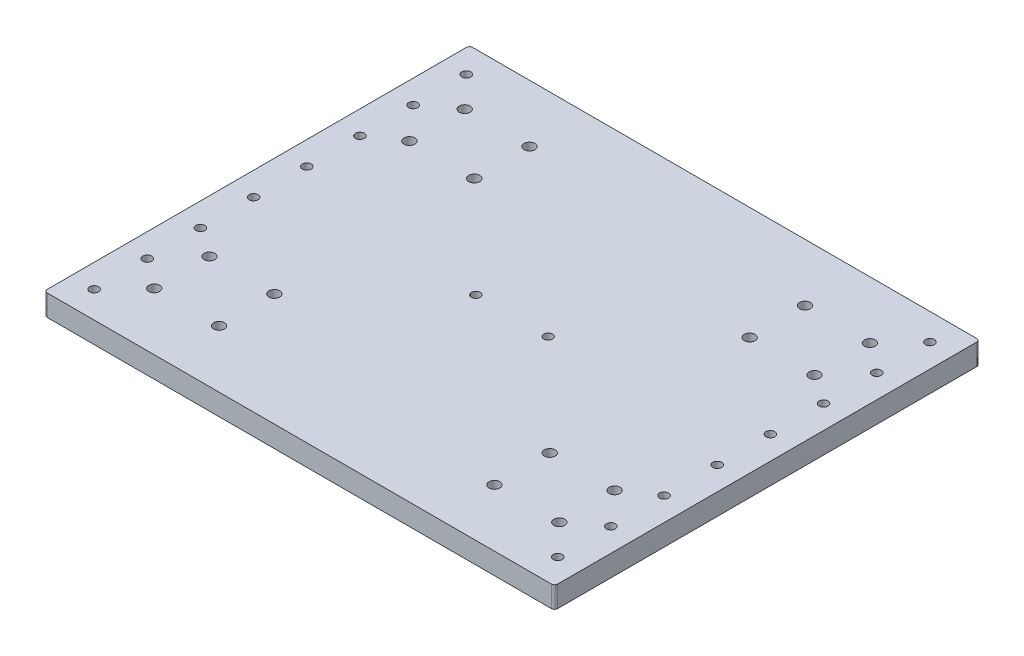
SolidWorks part; units mm, degrees
ref_plane "Front Plane" through (0, 0, 0) normal (0, 0, 1) x (1, 0, 0)
ref_plane "Top Plane" through (0, 0, 0) normal (0, 1, 0) x (1, 0, 0)
ref_plane "Right Plane" through (0, 0, 0) normal (1, 0, 0) x (0, 0, -1)
sketch "Sketch1" plane through (0, 0, 0) normal (0, 1, 0) x (1, 0, 0)
  line L1 (-120, -100) -> (120, -100)
  line L2 (-120, -100) -> (-120, 100)
  line L3 (-120, 100) -> (120, 100)
  line L4 (120, -100) -> (120, 100)
  line L5 (-120, -100) -> (120, 100) construction
  line L6 (-120, 100) -> (120, -100) construction
  point P0 (0, 0)
  dimension "D1" = 240
  dimension "D2" = 200
extrude "Boss-Extrude1" add sketch "Sketch1" along normal mid plane 10
sketch "Sketch2" plane through (0, 5, 0) normal (0, 1, 0) x (1, 0, 0)
  line L5 (-80, 100) -> (-80, -100)
  line L6 (-80, 100) -> (-80, -100) construction
  line L8 (80, -100) -> (80, 100)
  line L9 (80, -100) -> (80, 100) construction
  line L11 (120, 60) -> (-120, 60)
  line L12 (120, 60) -> (-120, 60) construction
  line L14 (-120, -60) -> (120, -60)
  line L15 (-120, -60) -> (120, -60) construction
  line L16 (-95.25, 73) -> (-64.75, 73) construction
  line L17 (-95.25, 73) -> (-95.25, 47) construction
  line L18 (-95.25, 47) -> (-64.75, 47) construction
  line L19 (-64.75, 73) -> (-64.75, 47) construction
  line L20 (-95.25, 73) -> (-64.75, 47) construction
  line L21 (-95.25, 47) -> (-64.75, 73) construction
  line L22 (64.75, 47) -> (95.25, 47) construction
  line L23 (64.75, 47) -> (64.75, 73) construction
  line L24 (64.75, 73) -> (95.25, 73) construction
  line L25 (95.25, 47) -> (95.25, 73) construction
  line L26 (64.75, 47) -> (95.25, 73) construction
  line L27 (64.75, 73) -> (95.25, 47) construction
  line L28 (64.75, -47) -> (95.25, -47) construction
  line L29 (64.75, -47) -> (64.75, -73) construction
  line L30 (64.75, -73) -> (95.25, -73) construction
  line L31 (95.25, -47) -> (95.25, -73) construction
  line L32 (64.75, -47) -> (95.25, -73) construction
  line L33 (64.75, -73) -> (95.25, -47) construction
  line L34 (-95.25, -73) -> (-64.75, -73) construction
  line L35 (-95.25, -73) -> (-95.25, -47) construction
  line L36 (-95.25, -47) -> (-64.75, -47) construction
  line L37 (-64.75, -73) -> (-64.75, -47) construction
  line L38 (-95.25, -73) -> (-64.75, -47) construction
  line L39 (-95.25, -47) -> (-64.75, -73) construction
  circle A0 centre (-95.25, 73) radius 2.55
  circle A1 centre (-95.25, 47) radius 2.55
  circle A2 centre (-64.75, 73) radius 2.55
  circle A3 centre (-64.75, 47) radius 2.55
  circle A4 centre (-95.25, -47) radius 2.55
  circle A5 centre (-95.25, -73) radius 2.55
  circle A6 centre (-64.75, -73) radius 2.55
  circle A7 centre (-64.75, -47) radius 2.55
  circle A8 centre (95.25, -47) radius 2.55
  circle A9 centre (64.75, -47) radius 2.55
  circle A10 centre (64.75, -73) radius 2.55
  circle A11 centre (95.25, -73) radius 2.55
  circle A12 centre (64.75, 73) radius 2.55
  circle A13 centre (64.75, 47) radius 2.55
  circle A14 centre (95.25, 73) radius 2.55
  circle A15 centre (95.25, 47) radius 2.55
  point P0 (-80, 60)
  point P13 (80, 60)
  point P18 (80, -60)
  point P23 (-80, -60)
  dimension "D13" = 5.1
  dimension "D14" = 5.1
  dimension "D15" = 5.1
  dimension "D16" = 5.1
  dimension "D17" = 5.1
  dimension "D18" = 5.1
  dimension "D19" = 5.1
  dimension "D20" = 5.1
  dimension "D21" = 5.1
  dimension "D22" = 5.1
  dimension "D23" = 5.1
  dimension "D24" = 5.1
  dimension "D25" = 5.1
  dimension "D26" = 5.1
  dimension "D27" = 5.1
  dimension "D28" = 5.1
  dimension "D1" = 40
  dimension "D5" = 30.5
  dimension "D6" = 26
  dimension "D7" = 30.5
  dimension "D8" = 26
  dimension "D9" = 26
  dimension "D10" = 30.5
  dimension "D11" = 26
  dimension "D12" = 30.5
  dimension "D2" = 40
  dimension "D3" = 40
  dimension "D4" = 40
extrude "Cut-Extrude1" cut sketch "Sketch2" against normal through all
sketch "Sketch3" plane through (0, 5, 0) normal (0, 1, 0) x (1, 0, 0)
  line L3 (-17, 0) -> (17, 0) construction
  circle A0 centre (-17, 0) radius 2.05
  circle A1 centre (17, 0) radius 2.05
  point P0 (0, 0)
  dimension "D3" = 4.1
  dimension "D4" = 4.1
  dimension "D1" = 34
extrude "Cut-Extrude2" cut sketch "Sketch3" against normal through all
hole_wizard "M5x0.8 Tapped Hole1" positions "Sketch7" profile "Sketch5" tap size "M5x0.8" standard "ANSI Metric" end condition through all
sketch "Sketch7" plane through (0, 5, 0) normal (0, 1, 0) x (1, 0, 0)
  line L0 (120, 100) -> (-120, 100) construction
  line L1 (-120, 100) -> (-120, -100) construction
  line L2 (120, -100) -> (120, 100) construction
  point P0 (-109, 87.5)
  point P2 (109, 87.5)
  dimension "D1" = 12.5
  dimension "D2" = 11
  dimension "D3" = 11
  dimension "D4" = 12.5
sketch "Sketch5" plane through (-109, 5, -87.5) normal (1, 0, 0) x (0, 0, 1)
  line L0 (0, 0) -> (0, 10)
  line L1 (0, 10) -> (2.1, 10)
  line L2 (2.1, 10) -> (2.1, 0)
  line L5 (2.1, 0) -> (0, 0)
  line L11 (0, -6.35) -> (0, 107.95) construction
  dimension "Thru Tap Drill Dia." = 4.2
  dimension "Thru Tap Drill Depth" = 10
cosmetic thread "Hole Thread1" parameters "D2"=5
cosmetic thread "Hole Thread2" parameters "D2"=5
fillet "Fillet1" radius 1.5 4 edges at (-120, 0, -100) (120, 0, -100) (-120, 0, 100) (120, 0, 100)
pattern_linear "LPattern2" count 8 spacing 25 along (0, 0, 1) of "M5x0.8 Tapped Hole1"
